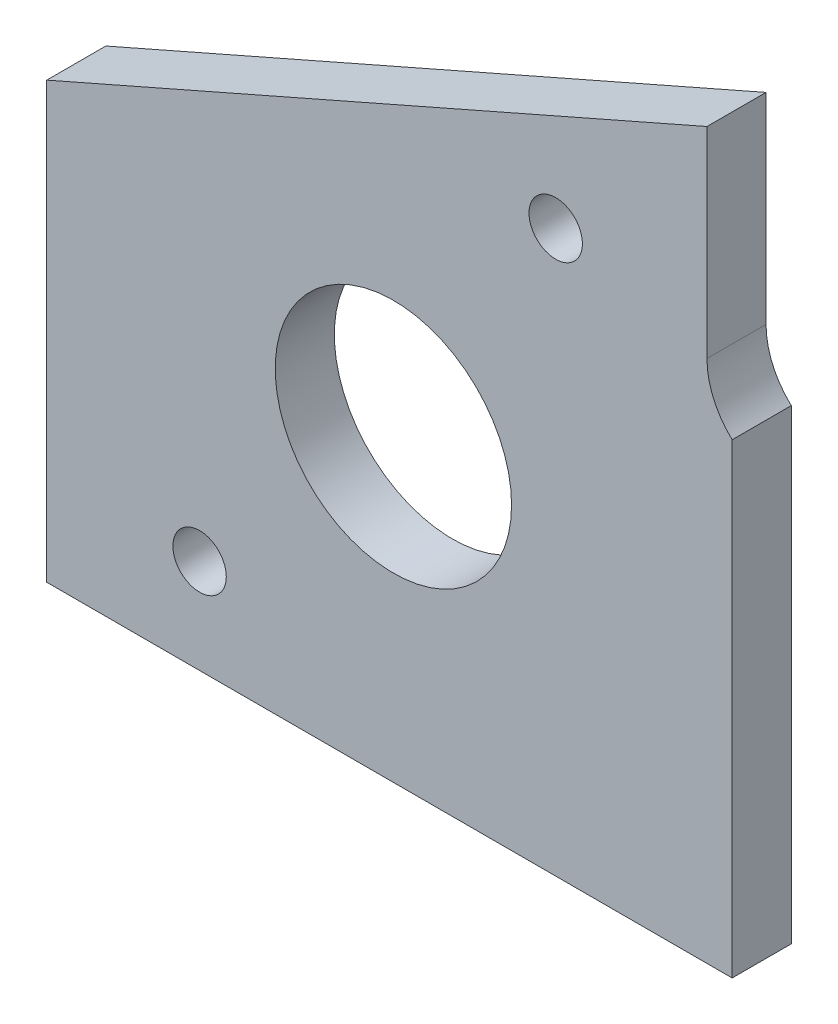
SolidWorks part; units mm, degrees
ref_plane "Front Plane" through (0, 0, 0) normal (0, 0, 1) x (1, 0, 0)
ref_plane "Top Plane" through (0, 0, 0) normal (0, 1, 0) x (1, 0, 0)
ref_plane "Right Plane" through (0, 0, 0) normal (1, 0, 0) x (0, 0, -1)
sketch "Sketch1" plane through (0, 0, 0) normal (0, 0, 1) x (1, 0, 0)
  line L10 (-13.97, 22.86) -> (-13.97, 60.4316)
  line L11 (-16.002, 65.0875) -> (-16.002, 81.28)
  line L12 (-16.002, 81.28) -> (-69.215, 57.912)
  line L13 (-69.215, 57.912) -> (-69.215, 22.86)
  line L14 (-69.215, 22.86) -> (-13.97, 22.86)
  arc A2 (-16.002, 65.0875) -> (-13.97, 60.4316) centre (-9.652, 65.0875) ccw
extrude "Boss-Extrude1" add sketch "Sketch1" along normal blind 4.7625
hole_wizard "3/4 (0.75) Diameter Hole1" positions "Sketch3" profile "Sketch2" hole size "3/4" standard "ANSI Inch" end condition through all
sketch "Sketch3" plane through (0, 0, 4.7625) normal (0, 0, 1) x (1, 0, 0)
  point P0 (-41.275, 46.99)
sketch "Sketch2" plane through (-41.275, 46.99, 4.7625) normal (1, 0, 0) x (0, -1, 0)
  line L0 (0, 0) -> (0, 4.7625)
  line L1 (0, 4.7625) -> (9.525, 4.7625)
  line L2 (9.525, 4.7625) -> (9.525, 0)
  line L5 (9.525, 0) -> (0, 0)
  line L11 (0, -6.35) -> (0, 107.95) construction
  dimension "Thru Hole Dia." = 19.05
  dimension "Thru Hole Depth" = 4.7625
hole_wizard "#6 Clearance Hole1" positions "Sketch5" profile "Sketch4" hole size "#6" standard "ANSI Inch" end condition through all
sketch "Sketch5" plane through (0, 0, 4.7625) normal (0, 0, 1) x (1, 0, 0)
  point P0 (-56.896, 30.48)
  point P3 (-28.194, 68.072)
sketch "Sketch4" plane through (-56.896, 30.48, 4.7625) normal (1, 0, 0) x (0, -1, 0)
  line L0 (0, 0) -> (0, 4.7625)
  line L1 (0, 4.7625) -> (2.1526, 4.7625)
  line L2 (2.1526, 4.7625) -> (2.1526, 0)
  line L5 (2.1526, 0) -> (0, 0)
  line L11 (0, -6.35) -> (0, 107.95) construction
  dimension "Thru Hole Dia." = 4.3053
  dimension "Thru Hole Depth" = 4.7625
